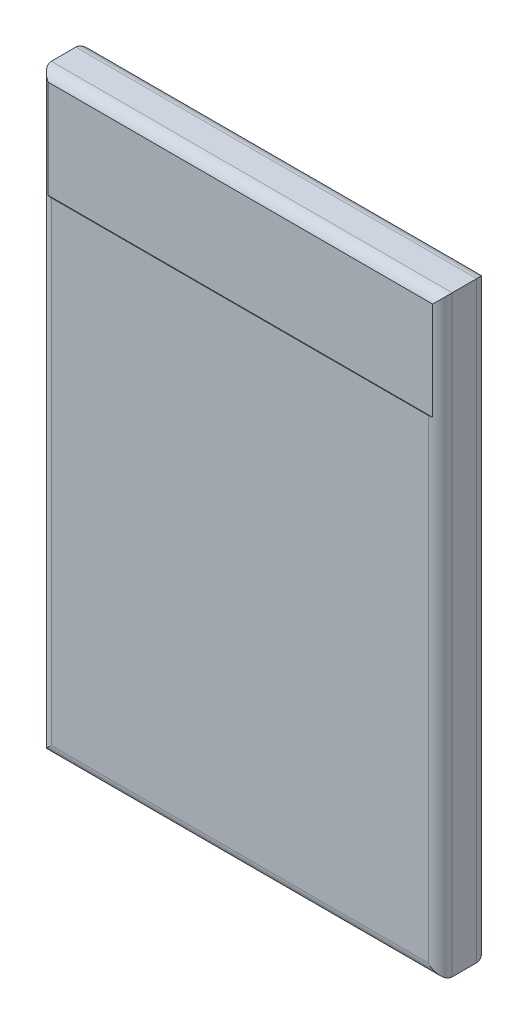
SolidWorks part; units mm, degrees
material "Alliage 1060"
ref_plane "Plan de face" through (0, 0, 0) normal (0, 0, 1) x (1, 0, 0)
ref_plane "Plan de dessus" through (0, 0, 0) normal (0, 1, 0) x (1, 0, 0)
ref_plane "Plan de droite" through (0, 0, 0) normal (1, 0, 0) x (0, 0, -1)
sketch "Esquisse1" plane through (0, 0, 0) normal (0, 0, 1) x (1, 0, 0)
  line L1 (-33.5, -49.5) -> (33.5, -49.5)
  line L2 (-33.5, -49.5) -> (-33.5, 49.5)
  line L3 (-33.5, 49.5) -> (33.5, 49.5)
  line L4 (33.5, -49.5) -> (33.5, 49.5)
  line L5 (-33.5, -49.5) -> (33.5, 49.5) construction
  line L6 (-33.5, 49.5) -> (33.5, -49.5) construction
  point P0 (0, 0)
  dimension "D1" = 67
  dimension "D2" = 99
extrude "Boss.-Extru.1" add sketch "Esquisse1" along normal blind 4.05 and the other way blind 4.05
sketch "Esquisse2" plane through (0, 0, 4.05) normal (0, 0, 1) x (1, 0, 0)
  line L0 (33.5, -49.5) -> (33.5, 49.5) construction
  line L1 (-33.5, 49.5) -> (33.5, 49.5)
  line L2 (-33.5, 49.5) -> (-33.5, 31.7454)
  line L3 (-33.5, 31.7454) -> (33.5, 31.7454)
  line L4 (33.5, 49.5) -> (33.5, 31.7454)
fillet "Congé1" radius 2 8 edges at (0, -49.5, -4.05) (33.5, 0, -4.05) (-33.5, 0, -4.05) (0, -49.5, 4.05) (-33.5, 0, 4.05) (33.5, 0, 4.05) (0, 49.5, -4.05) (0, 49.5, 4.05)
extrude "Enlèv. mat.-Extru.5" cut sketch "Esquisse2" against normal blind 0.1
sketch "Esquisse6" plane through (0, 0, -4.05) normal (0, 0, -1) x (-1, 0, 0)
  line L1 (-32.1245, 31.7454) -> (32.1245, 31.7454)
  line L2 (-32.1245, 31.7454) -> (-32.1245, 48.1245)
  line L3 (-32.1245, 48.1245) -> (32.1245, 48.1245)
  line L4 (32.1245, 31.7454) -> (32.1245, 48.1245)
extrude "Enlèv. mat.-Extru.6" cut sketch "Esquisse6" against normal blind 0.1
sketch "Esquisse7" plane through (0, 0, -4.05) normal (0, 0, -1) x (-1, 0, 0)
  text T0 "6000 mAh"
extrude "Enlèv. mat.-Extru.7" cut sketch "Esquisse7" against normal blind 0.1
